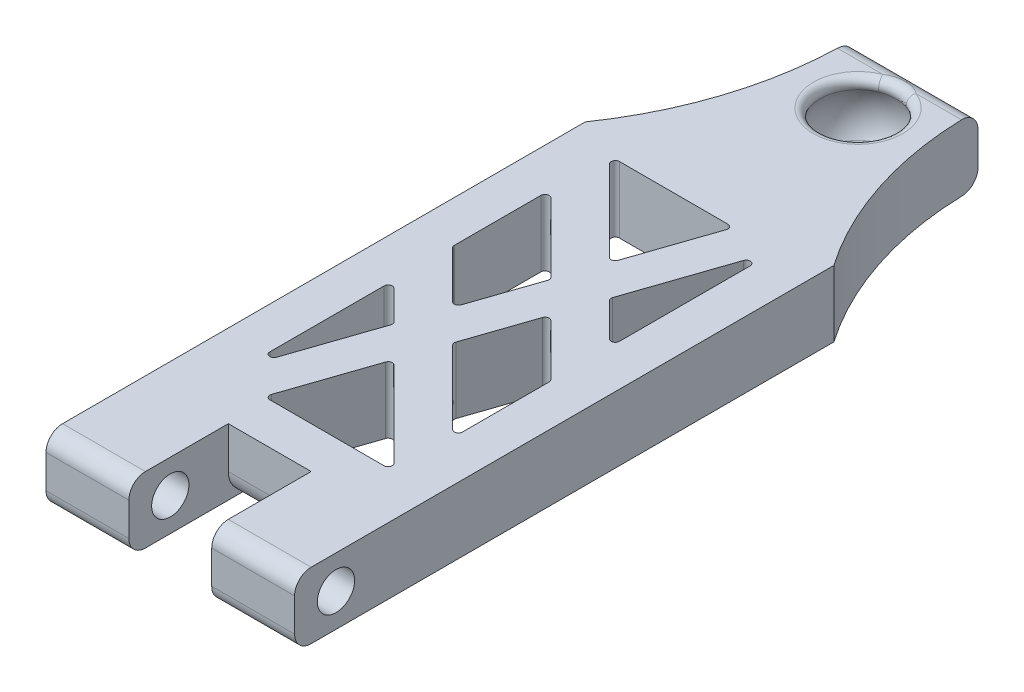
SolidWorks part; units mm, degrees
ref_plane "Front Plane" through (0, 0, 0) normal (0, 0, 1) x (1, 0, 0)
ref_plane "Top Plane" through (0, 0, 0) normal (0, 1, 0) x (1, 0, 0)
ref_plane "Right Plane" through (0, 0, 0) normal (1, 0, 0) x (0, 0, -1)
sketch "Sketch1" plane through (0, 0, 0) normal (0, 1, 0) x (1, 0, 0)
  line L1 (-15, 45) -> (15, 45)
  line L2 (-15, 45) -> (-15, -45)
  line L3 (-15, -45) -> (15, -45)
  line L4 (15, 45) -> (15, -45)
  line L5 (-15, 45) -> (15, -45) construction
  line L6 (-15, -45) -> (15, 45) construction
  point P0 (0, 0)
  dimension "D1" = 30
  dimension "D2" = 90
extrude "Boss-Extrude1" add sketch "Sketch1" along normal blind 8
sketch "Sketch2" plane through (0, 8, 0) normal (0, 1, 0) x (1, 0, 0)
  line L5 (-15, -45) -> (15, -45) construction
  line L6 (5, -45) -> (-5, -45)
  line L7 (5, -45) -> (5, -33)
  line L8 (5, -33) -> (-5, -33)
  line L9 (-5, -45) -> (-5, -33)
  line L10 (15, -45) -> (15, 45) construction
  dimension "D1" = 10
  dimension "D5" = 12
  dimension "D6" = 10
extrude "Cut-Extrude1" cut sketch "Sketch2" against normal blind 8
sketch "Sketch3" plane through (15, 0, 0) normal (1, 0, 0) x (0, 0, -1)
  line L0 (-45, 8) -> (-45, 0) construction
  line L1 (-45, 8) -> (45, 8) construction
  circle A0 centre (-40, 4) radius 2.25
  dimension "D1" = 4.5
  dimension "D2" = 5
  dimension "D3" = 4
extrude "Cut-Extrude2" cut sketch "Sketch3" against normal through all
fillet "Fillet1" radius 2 6 edges at (0, 0, -45) (0, 8, -45) (-10, 8, 45) (-10, 0, 45) (10, 0, 45) (10, 8, 45)
sketch "Sketch4" plane through (0, 8, 0) normal (0, 1, 0) x (1, 0, 0)
  line L0 (5, 18) -> (-10, 18)
  line L1 (-10, 18) -> (1.1864, 6.8136)
  line L2 (10, -2) -> (10, 18)
  line L3 (-10, -8) -> (-10, -26)
  line L4 (-5.6818, -28) -> (10, -28)
  line L5 (10, -28) -> (-1.6949, -16.3051)
  line L6 (15, -43) -> (15, 43) construction
  line L7 (-15, 43) -> (-15, -43) construction
  line L8 (-10, 10.9289) -> (-10, -0.9289)
  line L9 (-10, -0.9289) -> (-3.626, -7.3029)
  line L10 (10.0023, -20.9312) -> (10.0023, -9.0734)
  line L11 (10.0023, -9.0734) -> (3.1175, -2.1886)
  line L13 (5, -33) -> (-5, -33) construction
  line L14 (5, 18) -> (1.1864, 6.8136)
  line L15 (-5.6818, -28) -> (-1.6949, -16.3051)
  line L16 (0.1028, -11.0317) -> (3.1175, -2.1886)
  line L18 (4.9153, 3.0847) -> (10, -2)
  line L19 (-0.6113, 1.5402) -> (-10, 10.9289)
  line L20 (0.1028, -11.0317) -> (10.0023, -20.9312)
  line L21 (-5.4237, -12.5763) -> (-10, -8)
  line L22 (-5.4237, -12.5763) -> (-10, -26)
  line L23 (-0.6113, 1.5402) -> (-3.626, -7.3029)
  line L24 (4.9153, 3.0847) -> (10, 18)
  dimension "D1" = 5
  dimension "D2" = 5
  dimension "D3" = 5
  dimension "D4" = 45
  dimension "D5" = 45
  dimension "D6" = 5
  dimension "D7" = 5
  dimension "D8" = 46
  dimension "D9" = 5
  dimension "D10" = 20
  dimension "D11" = 18
  dimension "D12" = 15
  dimension "D13" = 14
extrude "Cut-Extrude3" cut sketch "Sketch4" against normal through all
fillet "Fillet2" radius 3 1 edges at (0, 0, 33)
sketch "Sketch5" plane through (0, 0, 0) normal (1, 0, 0) x (0, 0, -1)
  line L0 (-43, 8) -> (43, 8) construction
  line L1 (-43, 0) -> (43, 0) construction
  line L2 (41.5, 8) -> (38, 8)
  line L3 (38, 8) -> (38, 0)
  line L4 (38, 0) -> (41.5, 0)
  arc A2 (41.5, 0) -> (41.5, 8) centre (38, 4) ccw
  dimension "D1" = 3.5
  dimension "D2" = 38
  dimension "D4" = 8
revolve "Cut-Revolve1" cut sketch "Sketch5" angle 360 about L3
fillet "Fillet3" radius 0.9 2 edges at (0, 0, -34.5) (0, 8, -34.5)
sketch "Sketch6" plane through (0, 8, 0) normal (0, 1, 0) x (1, 0, 0)
  line L0 (-15, 45) -> (15, 45) construction
  line L1 (-15, 43) -> (-15, -43) construction
  line L2 (-7.4775, 45) -> (-15, 45)
  line L3 (-15, 45) -> (-15, 20.0808)
  line L4 (0, -4.4) -> (0, 4.4) construction
  line L5 (15, 45) -> (15, 20.0808)
  line L6 (7.4775, 45) -> (15, 45)
  arc A0 (-7.4775, 45) -> (-15, 20.0808) centre (-49.7917, 44.1785) cw
  arc A1 (7.4775, 45) -> (15, 20.0808) centre (49.7917, 44.1785) ccw
extrude "Cut-Extrude4" cut sketch "Sketch6" against normal through all both and the other way through all
fillet "Fillet4" radius 0.5 20 edges at (5, 4, -18) (1.1864, 4, -6.8136) (-10, 4, -18) (10, 4, 2) (4.9153, 4, -3.0847) (10, 4, -18) (-10, 4, 0.9289) (-10, 4, -10.9289) (-0.6113, 4, -1.5402) (-3.626, 4, 7.3029) (0.1028, 4, 11.0317) (3.1175, 4, 2.1886) (10.0023, 4, 9.0734) (10.0023, 4, 20.9312) (10, 4, 28) (-5.6818, 4, 28) (-1.6949, 4, 16.3051) (-10, 4, 8) (-5.4237, 4, 12.5763) (-10, 4, 26)
